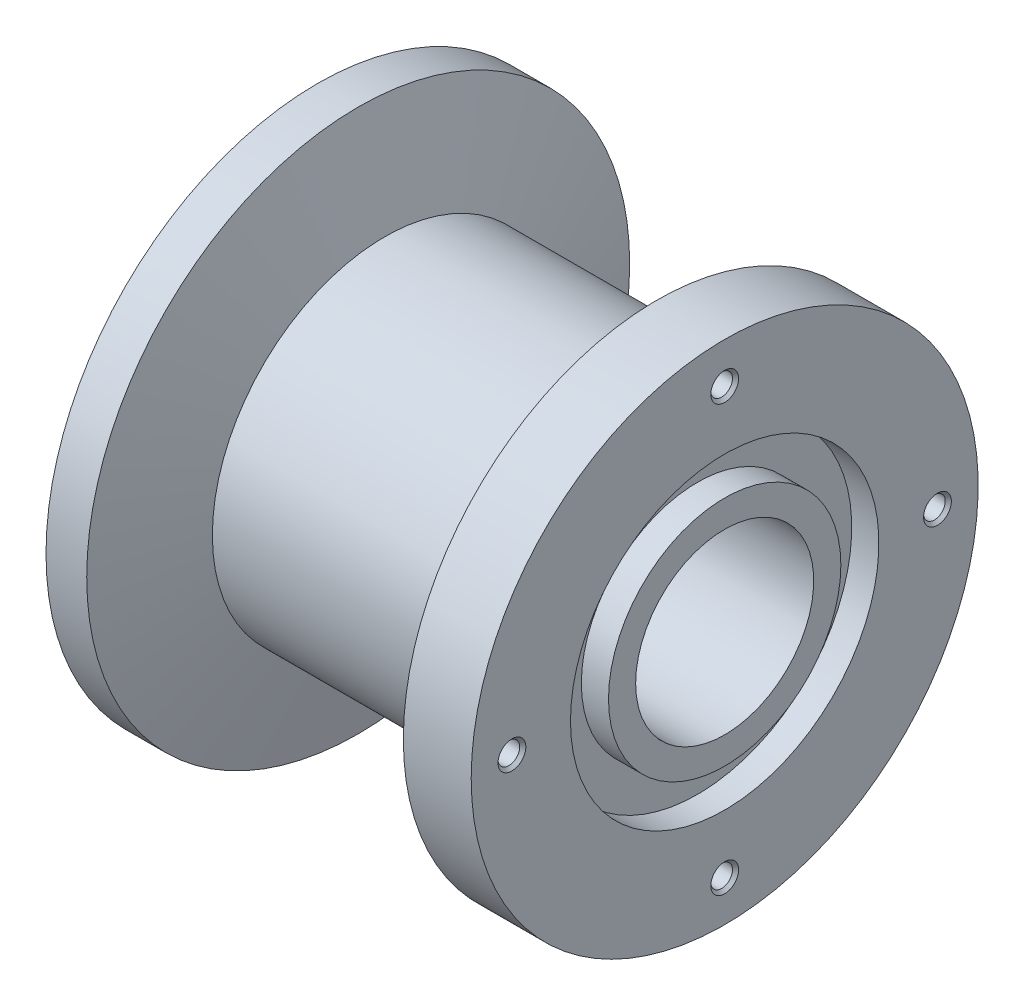
SolidWorks part; units mm, degrees
material "AISI 304"
ref_plane "Спереди" through (0, 0, 0) normal (0, 0, 1) x (1, 0, 0)
ref_plane "Сверху" through (0, 0, 0) normal (0, 1, 0) x (1, 0, 0)
ref_plane "Справа" through (0, 0, 0) normal (1, 0, 0) x (0, 0, -1)
ref_axis "Ось1" through (0, 0, 0) along (1, 0, 0)
sketch "Эскиз1" plane through (0, 0, 0) normal (0, 0, 1) x (1, 0, 0)
  line L0 (-29.0412, 0) -> (34.6413, 0) construction
  line L1 (0, 20) -> (0, 13.2)
  line L2 (0, 13.2) -> (2.7, 13.2)
  line L3 (2.7, 13.2) -> (2.7, 6.56)
  line L4 (2.7, 6.56) -> (30, 6.56)
  line L5 (30, 6.56) -> (30, 8.56)
  line L6 (30, 8.56) -> (28, 8.56)
  line L7 (28, 8.56) -> (28, 11.36)
  line L8 (28, 11.36) -> (30, 11.36)
  line L9 (30, 11.36) -> (30, 18.675)
  line L10 (30, 18.675) -> (25, 18.675)
  line L11 (25, 18.675) -> (25, 12.7)
  line L12 (25, 12.7) -> (4.956, 12.7)
  line L13 (4.956, 12.7) -> (3, 20)
  line L14 (3, 20) -> (0, 20)
  line L15 (30, 15.675) -> (25, 15.675) construction
  dimension "D1" = 40
  dimension "D2" = 2.7
  dimension "D3" = 15
  dimension "D4" = 13.12
  dimension "D5" = 26.4
  dimension "D6" = 25.4
  dimension "D7" = 37.35
  dimension "D8" = 3
  dimension "D9" = 5
  dimension "D10" = 30
  dimension "D11" = 22.72
  dimension "D12" = 17.12
  dimension "D13" = 2
  dimension "D14" = 31.35
revolve "Повернуть1" add sketch "Эскиз1" angle 360 about L0
hole_wizard "Отверстие обработанное метчиком M21" positions "Эскиз2" profile "Эскиз3" tap size "M2" standard "ISO" end condition up to next
sketch "Эскиз2" plane through (30, 0, 0) normal (1, 0, 0) x (0, 0, -1)
  point P0 (0, 15.675)
sketch "Эскиз3" plane through (30, 15.675, 0) normal (0, 1, 0) x (0, 0, -1)
  line L0 (0, 0) -> (0, 5)
  line L1 (0, 5) -> (0.8, 5)
  line L2 (0.8, 5) -> (0.8, 0.225)
  line L3 (0.8, 0.225) -> (1.025, 0)
  line L5 (1.025, 0) -> (0, 0)
  line L6 (-0.8, 0.225) -> (-1.025, 0) construction
  line L11 (0, -6.35) -> (0, 107.95) construction
  dimension "Диаметр проходного сверла" = 1.6
  dimension "Глубина проходного сверла" = 5
  dimension "Диаметр передней зенковки" = 2.05
  dimension "Угол передней зенковки" = 90
cosmetic thread "Отверстие резьбы1" parameters "D2"=2
pattern_circular "Круговой массив1" count 4 over 360 about axis through (0, 0, 0) along (1, 0, 0) of "Отверстие обработанное метчиком M21"
